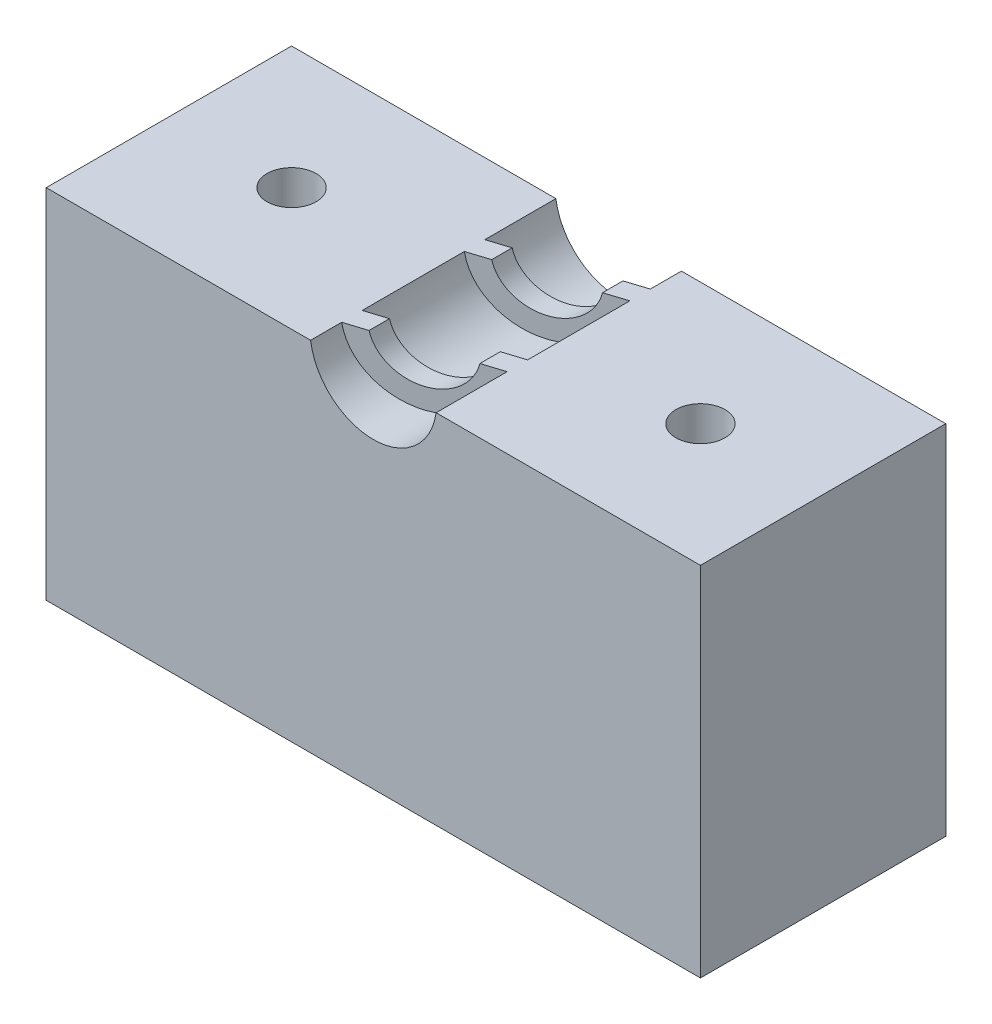
SolidWorks part; units mm, degrees
ref_plane "前视基准面" through (0, 0, 0) normal (0, 0, 1) x (1, 0, 0)
ref_plane "上视基准面" through (0, 0, 0) normal (0, 1, 0) x (1, 0, 0)
ref_plane "右视基准面" through (0, 0, 0) normal (1, 0, 0) x (0, 0, -1)
other "Configuration Table"
sketch "草图1" plane through (0, 0, 0) normal (0, 0, 1) x (1, 0, 0)
  line L1 (-8, -8) -> (8, -8)
  line L2 (-8, -8) -> (-8, 8)
  line L3 (-8, 8) -> (8, 8)
  line L4 (8, -8) -> (8, 8)
  line L5 (-8, -8) -> (8, 8) construction
  line L6 (-8, 8) -> (8, -8) construction
  circle A0 centre (0, 0) radius 1.55
  point P0 (0, 0)
  dimension "D3" = 3.1
  dimension "D1" = 16
  dimension "D2" = 16
extrude "凸台-拉伸1" add sketch "草图1" along normal mid plane 6
sketch "草图6" plane through (0, 0, 0) normal (0, 1, 0) x (1, 0, 0)
  line L0 (-1.55, -3) -> (1.55, -3) construction
  line L1 (1.55, 3) -> (-1.55, 3) construction
  line L2 (-1.55, -3) -> (1.55, -3)
  line L3 (1.55, 3) -> (-1.55, 3)
  line L4 (-1.55, 3) -> (-1.55, -3)
  line L5 (1.55, -3) -> (1.55, 3)
  line L6 (-1.55, 0.7565) -> (1.55, 1.7435)
  line L7 (1.55, 1.7435) -> (1.55, 2.2435)
  line L8 (1.55, 2.2435) -> (-1.55, 1.2565)
  line L9 (-1.55, -1.7435) -> (1.55, -0.7565)
  line L10 (-1.55, -2.2435) -> (1.55, -1.2565)
  line L11 (-2.0945, -0.6668) -> (3.135, 0.9981) construction
  line L12 (-3.1004, 0) -> (4.2723, 0) construction
  dimension "D1" = 2.5
  dimension "D2" = 0.5
  dimension "D3" = 0.5
  dimension "D4" = 17.66
extrude "凸台-拉伸2" add sketch "草图6" against normal up to surface (8 mm away) contours L4 L10 L5 L9 | L5 L8 L4 L6 region at (0, 0, 1.5) region at (0, 0, -1.5) up to face at (0, -8, 0)
sketch "草图7" plane through (0, 0, 0) normal (0, 0, 1) x (1, 0, 0)
  line L0 (0, 0) -> (-1.0279, -0.2141)
  line L1 (0, 0) -> (1.0279, -0.2141)
  line L2 (-1.0279, -0.2141) -> (-8, -0.2141)
  line L3 (1.0279, -0.2141) -> (8, -0.2141)
  line L6 (8, -8) -> (8, 8)
  line L7 (-8, -8) -> (8, -8)
  line L8 (-8, 8) -> (-8, -8)
  line L9 (8, 8) -> (-8, 8)
  line L10 (8, -8) -> (8, 8)
  line L11 (-8, -8) -> (8, -8)
  line L12 (-8, 8) -> (-8, -8)
  line L13 (8, 8) -> (-8, 8)
  circle A0 centre (0, 0) radius 1.05
  dimension "D1" = 2.1
  dimension "D2" = 0
  dimension "D3" = 156.47
extrude "切除-拉伸2" cut sketch "草图7" against normal through all both and the other way through all contours A0 L3 L10 L13 L12 L2 | L1 A0 L0 | L0 A0 L1 region at (0, -0.5019, 0) region at (0, 0.3858, 0) region at (0, 3.953, 0)
sketch "草图8" plane through (0, 0, 0) normal (0, 1, 0) x (1, 0, 0)
  line L0 (0, 5.5834) -> (0, -5.0797) construction
  circle A0 centre (-5, 0) radius 0.6
  circle A1 centre (5, 0) radius 0.6
  dimension "D2" = 1.2
  dimension "D3" = 10
extrude "切除-拉伸3" cut sketch "草图8" against normal through all
sketch "草图9" plane through (0, -8, 0) normal (0, -1, 0) x (1, 0, 0)
  line L4 (-8, -3) -> (8, -3)
  line L5 (8, -3) -> (8, 3)
  line L6 (8, 3) -> (-8, 3)
  line L7 (-8, 3) -> (-8, -3)
  line L8 (-8, -3) -> (8, -3)
  line L9 (8, -3) -> (8, 3)
  line L10 (8, 3) -> (-8, 3)
  line L11 (-8, 3) -> (-8, -3)
  circle A0 centre (-5, 0) radius 0.6 construction
  circle A1 centre (5, 0) radius 0.6 construction
  circle A2 centre (-5, 0) radius 0.6
  circle A3 centre (5, 0) radius 0.6
  dimension "D1" = 0
extrude "凸台-拉伸3" add sketch "草图9" along normal up to surface (0.955 mm away)
equation "\"x\"=0.8094"
